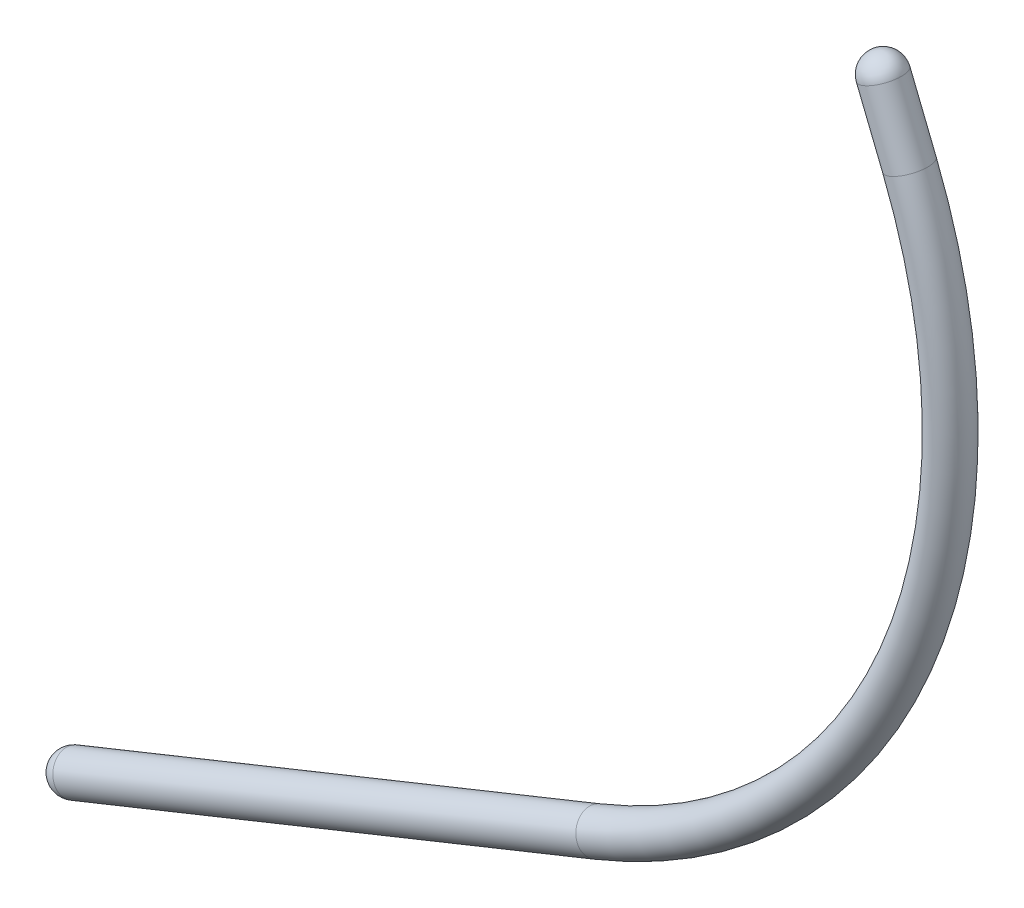
SolidWorks part; units mm, degrees
material "光敏树脂"
ref_plane "前视基准面" through (0, 0, 0) normal (0, 0, 1) x (1, 0, 0)
ref_plane "上视基准面" through (0, 0, 0) normal (0, 1, 0) x (1, 0, 0)
ref_plane "右视基准面" through (0, 0, 0) normal (1, 0, 0) x (0, 0, -1)
sketch "草图1" plane through (0, 0, 0) normal (0, 0, 1) x (1, 0, 0)
  line L0 (-20.3921, 75.3338) -> (-22.2588, 79.9723) construction
  line L1 (-57.5, 60.4005) -> (-20.3921, 75.3338) construction
  line L2 (-49.8178, 68.8817) -> (-73.0102, 59.5484) construction
  line L3 (-42.5667, 23.2926) -> (-79.6746, 8.3592) construction
  line L5 (-41.9693, 21.8082) -> (-79.0772, 6.8749)
  line L6 (-18.9078, 75.9311) -> (-20.7745, 80.5696)
  line L7 (-43.164, 24.7769) -> (-80.2719, 9.8435)
  line L8 (-21.8764, 74.7365) -> (-23.7431, 79.3749)
  line L9 (178.2731, -10.7234) -> (181.4731, -10.7234) construction
  line L10 (157.0515, -6.1234) -> (182.8731, -6.1234) construction
  line L11 (157.0515, -6.1234) -> (157.0515, -12.1234) construction
  line L12 (157.0515, -12.1234) -> (182.8731, -12.1234) construction
  line L13 (182.8731, -6.1234) -> (182.8731, -12.1234) construction
  line L14 (157.0515, -6.1234) -> (182.8731, -12.1234) construction
  line L15 (157.0515, -12.1234) -> (182.8731, -6.1234) construction
  line L16 (-18.1027, -23.8797) -> (19.2174, -38.2745) construction
  line L17 (19.2174, -38.2745) -> (20.5236, -38.7784) construction
  line L18 (20.5236, -38.7784) -> (19.8038, -40.6444) construction
  line L19 (19.8038, -40.6444) -> (17.0048, -39.5648) construction
  line L20 (17.0048, -39.5648) -> (18.4443, -35.8327) construction
  line L21 (18.4443, -35.8327) -> (21.2433, -36.9124) construction
  line L22 (21.2433, -36.9124) -> (20.5236, -38.7784) construction
  line L23 (181.4731, -10.7234) -> (181.4731, -7.5234) construction
  line L24 (179.6731, -9.3234) -> (179.6731, -9.4234) construction
  line L25 (178.2731, -10.7234) -> (178.2731, -7.5234) construction
  line L26 (178.2731, -7.5234) -> (181.4731, -7.5234) construction
  line L27 (179.6731, -14.4234) -> (179.6731, -12.1234) construction
  line L28 (157.0515, -59.1234) -> (208.5781, -59.1234) construction
  line L29 (159.542, -57.1234) -> (196.8805, -57.1234) construction
  line L30 (180.0731, -8.8234) -> (180.0731, -8.9234) construction
  arc A1 (-41.4467, 20.5095) -> (-17.2586, 75.5539) centre (-57.5, 60.4005) ccw construction
  arc A2 (-42.5667, 23.2926) -> (-20.3921, 75.3338) centre (-57.5, 60.4005) ccw construction
  arc A3 (-41.9693, 21.8082) -> (-18.9078, 75.9311) centre (-57.5, 60.4005) ccw
  arc A4 (-43.164, 24.7769) -> (-21.8764, 74.7365) centre (-57.5, 60.4005) ccw
  arc A5 (-20.7745, 80.5696) -> (-23.7431, 79.3749) centre (-22.2588, 79.9723) ccw
  arc A6 (-80.2719, 9.8435) -> (-79.0772, 6.8749) centre (-79.6746, 8.3592) ccw
  circle A8 centre (179.6731, -9.4234) radius 5 construction
  arc A9 (20.3151, -12.7412) -> (2.8846, -57.9316) centre (-18.1027, -23.8797) cw construction
  arc A10 (3.6192, -59.1234) -> (21.6598, -12.3513) centre (-18.1027, -23.8797) ccw construction
  arc A11 (2.1501, -56.7398) -> (18.9705, -13.131) centre (-18.1027, -23.8797) ccw construction
  arc A12 (2.1501, -56.7398) -> (3.6192, -59.1234) centre (2.8846, -57.9316) ccw construction
  arc A13 (21.6598, -12.3513) -> (18.9705, -13.131) centre (20.3151, -12.7412) ccw construction
  circle A14 centre (45.6195, -5.977) radius 1.4 construction
  circle A15 centre (179.6731, -9.3234) radius 1.4 construction
  circle A16 centre (179.6731, -9.4234) radius 1.5 construction
  circle A17 centre (180.3572, -35.6234) radius 21.5 construction
  circle A18 centre (180.0731, -8.9234) radius 1.4 construction
  circle A19 centre (180.0731, -8.8234) radius 1.5 construction
  circle A20 centre (180.0731, -8.8234) radius 5 construction
  point P0 (169.9623, -9.1234)
  point P1 (19.2174, -38.2745)
  dimension "D1" = 6
  dimension "D3" = 40
  dimension "D4" = 10
  dimension "D6" = 40
  dimension "D7" = 1.4
  dimension "D8" = 2.8
  dimension "D16" = 2.8
  dimension "D17" = 3
  dimension "D20" = 43
  dimension "D22" = 2.8
  dimension "D23" = 3
  dimension "D24" = 10
  dimension "D5" = 3.2
  dimension "D9" = 1.4
  dimension "D10" = 2
  dimension "D11" = 3
  dimension "D12" = 4
  dimension "D13" = 3
  dimension "D14" = 1.4
  dimension "D15" = 1.4
  dimension "D18" = 3.2
  dimension "D19" = 47
  dimension "D21" = 2
  dimension "D25" = 5
  dimension "D26" = 40
  dimension "D2" = 1.6
sketch "草图2" plane through (0, 0, 0) normal (0, 0, 1) x (1, 0, 0)
  line L0 (-20.3921, 75.3338) -> (-22.2588, 79.9723) construction
  line L1 (-42.5667, 23.2926) -> (-79.6746, 8.3592) construction
  line L2 (-20.3921, 75.3338) -> (-22.2588, 79.9723)
  line L3 (-42.5667, 23.2926) -> (-79.6746, 8.3592)
  arc A0 (-42.5667, 23.2926) -> (-20.3921, 75.3338) centre (-57.5, 60.4005) ccw construction
  arc A1 (-42.5667, 23.2926) -> (-20.3921, 75.3338) centre (-57.5, 60.4005) ccw
ref_plane "基准面1" through (-79.6746, 8.3592, 0) normal (-0.9277, -0.3733, 0) x (0, 0, 1)
sketch "草图3" plane through (-79.6746, 8.3592, 0) normal (-0.9277, -0.3733, 0) x (0, 0, 1)
  circle A0 centre (0, 0) radius 1.4
  dimension "D1" = 2.8
sweep "扫描1" add profiles "草图3" path "草图2"
sketch "草图4" plane through (-65.6746, -26.4294, 0) normal (-0.9277, -0.3733, 0) x (0, 0, 1)
  line L0 (0, 38.9) -> (0, 36.1)
  circle A1 centre (0, 37.5) radius 1.4
  arc A2 (0, 38.9) -> (0, 36.1) centre (0, 37.5) ccw
  dimension "D1" = 0
revolve "旋转1" add sketch "草图4" angle 360 about L0
sketch "草图6" plane through (-30.8, 76.535, 0) normal (-0.3733, 0.9277, 0) x (0.9277, 0.3733, 0)
  line L0 (7.8069, 0) -> (10.6069, 0)
  circle A1 centre (9.2069, 0) radius 1.4
  arc A2 (10.6069, 0) -> (7.8069, 0) centre (9.2069, 0) ccw
  dimension "D1" = 0
revolve "旋转2" add sketch "草图6" angle 360 about L0
sketch "草图7" plane through (0, 0, 0) normal (0, 0, 1) x (1, 0, 0)
  line L0 (-72.2522, 11.3462) -> (-56.4464, 17.707)
  line L1 (-42.5667, 23.2926) -> (-79.6746, 8.3592) construction
ref_axis "基准轴1" through (-72.2522, 11.3462, 0) along (0.9277, 0.3733, 0)
